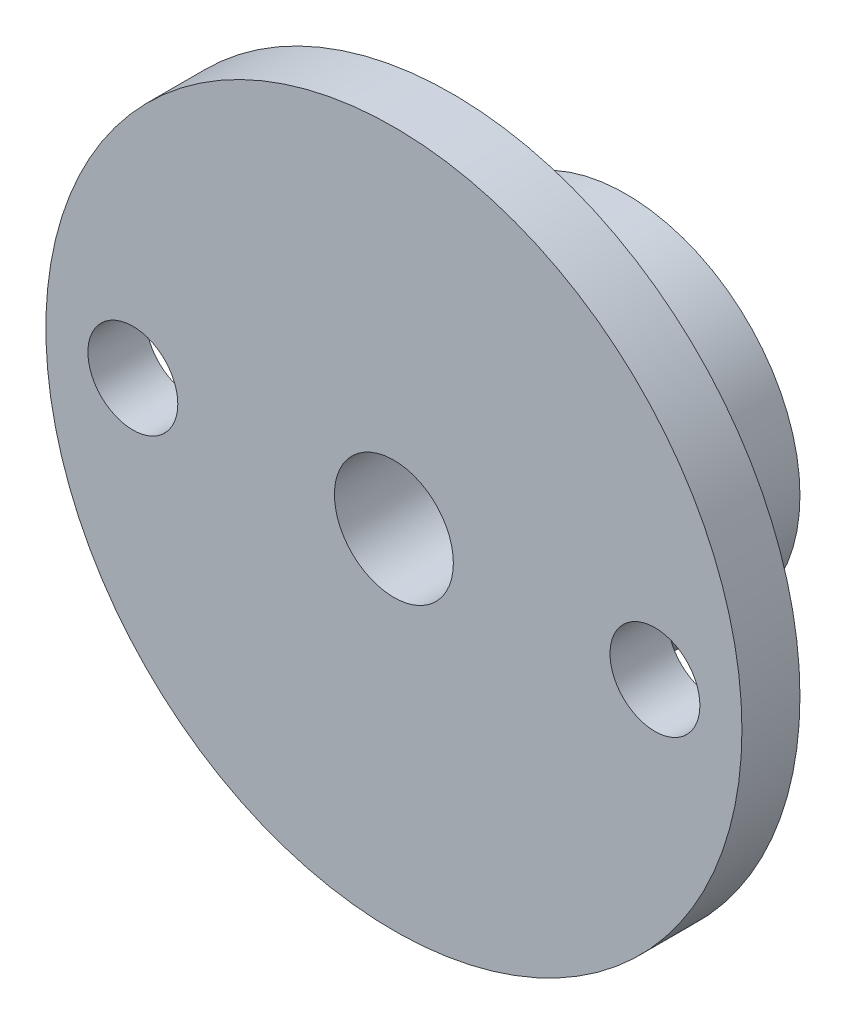
SolidWorks part; units mm, degrees
ref_plane "Plan de face" through (0, 0, 0) normal (0, 0, 1) x (1, 0, 0)
ref_plane "Plan de dessus" through (0, 0, 0) normal (0, 1, 0) x (1, 0, 0)
ref_plane "Plan de droite" through (0, 0, 0) normal (1, 0, 0) x (0, 0, -1)
sketch "Esquisse1" plane through (0, 0, 0) normal (0, 0, 1) x (1, 0, 0)
  circle A0 centre (0, 0) radius 6
extrude "Extrusion1" add sketch "Esquisse1" along normal blind 6
sketch "Esquisse2" plane through (0, 0, 6) normal (0, 0, 1) x (1, 0, 0)
  circle A0 centre (0, 0) radius 12
extrude "Extrusion2" add sketch "Esquisse2" along normal blind 2
sketch "Esquisse3" plane through (0, 0, 8) normal (0, 0, 1) x (1, 0, 0)
  circle A0 centre (0, 0) radius 2.05
extrude "Enlèv. mat.-Extru.1" cut sketch "Esquisse3" against normal through all
sketch "Esquisse4" plane through (0, 0, 8) normal (0, 0, 1) x (1, 0, 0)
  line L0 (-12.5775, 0) -> (13.3008, 0) construction
  circle A0 centre (0, 0) radius 9 construction
  circle A1 centre (-9, 0) radius 1.55
  circle A2 centre (9, 0) radius 1.55
extrude "Enlèv. mat.-Extru.2" cut sketch "Esquisse4" against normal through all
sketch "Esquisse5" plane through (0, 0, 0) normal (0, 1, 0) x (1, 0, 0)
  line L0 (-11.9961, -3) -> (12.555, -3) construction
  line L1 (0, 2.7795) -> (0, -9.7444) construction
  circle A0 centre (0, -3) radius 1.5
extrude "Enlèv. mat.-Extru.3" cut sketch "Esquisse5" against normal blind 10
ref_axis "Axe1" through (0, 0, 41.121) along (0, 0, -1)
